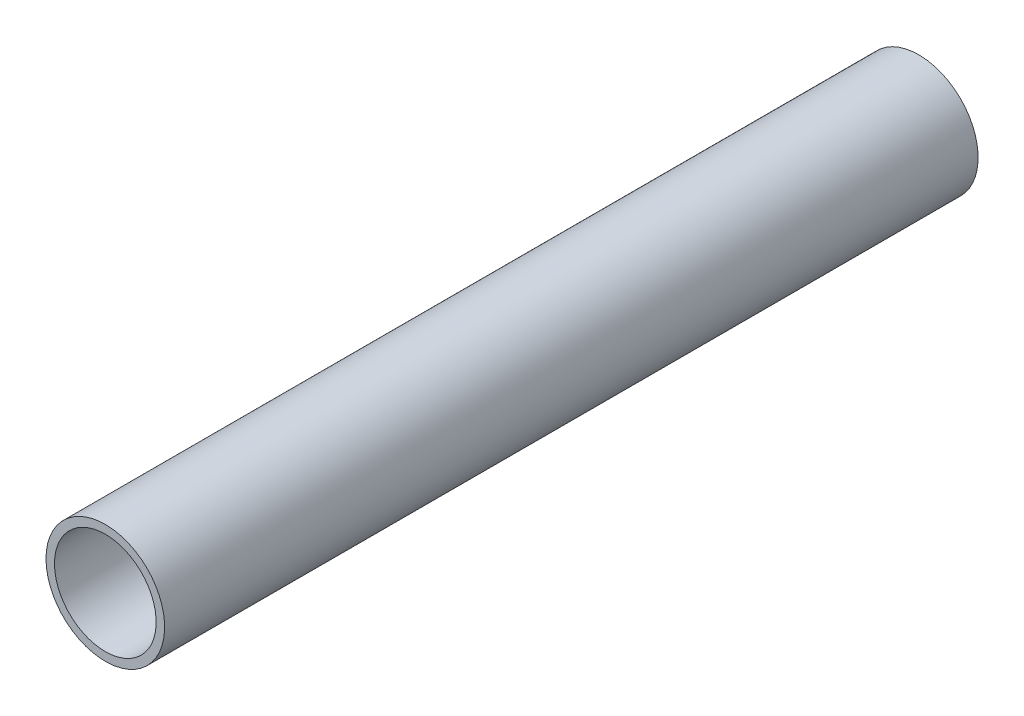
SolidWorks part; units mm, degrees
material "Thornel VCB-20 Carbon Cloth"
ref_plane "Front Plane" through (0, 0, 0) normal (0, 0, 1) x (1, 0, 0)
ref_plane "Top Plane" through (0, 0, 0) normal (0, 1, 0) x (1, 0, 0)
ref_plane "Right Plane" through (0, 0, 0) normal (1, 0, 0) x (0, 0, -1)
sketch "Sketch1" plane through (0, 0, 0) normal (0, 0, 1) x (1, 0, 0)
  circle A0 centre (0, 0) radius 9.525
  circle A1 centre (0, 0) radius 11.1125
  dimension "D1" = 19.05
  dimension "D2" = 22.225
extrude "Boss-Extrude1" add sketch "Sketch1" along normal mid plane 152.4
ref_axis "Axis1" through (0, 0, 76.2) along (0, 0, -1)
